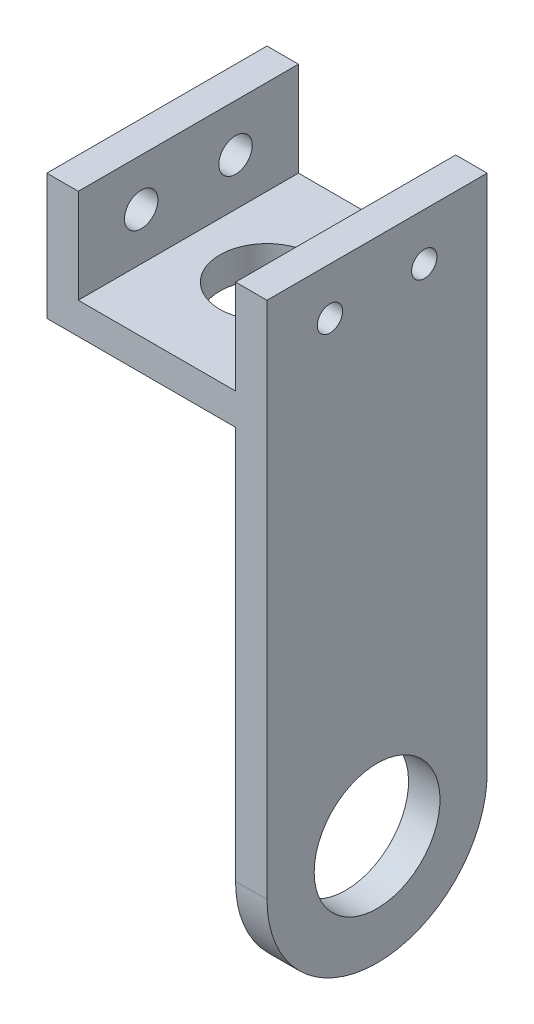
SolidWorks part; units mm, degrees
material "6061-T6 (SS)"
ref_plane "Front" through (0, 0, 0) normal (0, 0, 1) x (1, 0, 0)
ref_plane "Top" through (0, 0, 0) normal (0, 1, 0) x (1, 0, 0)
ref_plane "Right" through (0, 0, 0) normal (1, 0, 0) x (0, 0, -1)
sketch "Sketch1" plane through (0, 0, 0) normal (0, 0, 1) x (1, 0, 0)
  line L0 (0, 0) -> (6.35, 0)
  line L1 (6.35, 0) -> (6.35, 127)
  line L2 (6.35, 127) -> (0, 127)
  line L3 (0, 127) -> (0, 107.95)
  line L4 (0, 107.95) -> (-31.75, 107.95)
  line L5 (-31.75, 107.95) -> (-31.75, 127)
  line L6 (-31.75, 127) -> (-38.1, 127)
  line L7 (-38.1, 127) -> (-38.1, 101.6)
  line L8 (-38.1, 101.6) -> (0, 101.6)
  line L9 (0, 101.6) -> (0, 0)
  point P3 (3.175, 0)
  dimension "D1" = 6.35
  dimension "D2" = 101.6
  dimension "D3" = 31.75
  dimension "D4" = 6.35
  dimension "D5" = 6.35
  dimension "D6" = 19.05
  dimension "D7" = 19.05
  dimension "D8" = 6.35
extrude "Boss-Extrude1" add sketch "Sketch1" along normal blind 44.45
sketch "Sketch2" plane through (0, 0, 0) normal (-1, 0, 0) x (0, 0, 1)
  line L0 (44.45, 0) -> (0, 0) construction
  line L1 (44.45, 101.6) -> (44.45, 0) construction
  circle A0 centre (22.225, 22.225) radius 12.7
  dimension "D3" = 25.4
  dimension "D1" = 22.225
  dimension "D2" = 22.225
extrude "Cut-Extrude1" cut sketch "Sketch2" against normal blind 44.45
hole_wizard "1/4-20 Tapped Hole1" positions "Sketch3" profile "Sketch4" tap size "1/4-20" standard "ANSI Inch" end condition through all
sketch "Sketch3" plane through (0, 0, 0) normal (-1, 0, 0) x (0, 0, 1)
  line L2 (44.45, 127) -> (0, 127) construction
  line L3 (0, 127) -> (0, 107.95) construction
  point P0 (12.7, 117.475)
  point P2 (31.75, 117.475)
  dimension "D1" = 19.05
  dimension "D2" = 9.525
  dimension "D3" = 12.7
sketch "Sketch4" plane through (0, 117.475, 12.7) normal (0, 1, 0) x (0, 0, 1)
  line L0 (0, 0) -> (0, 6.35)
  line L1 (0, 6.35) -> (2.5527, 6.35)
  line L2 (2.5527, 6.35) -> (2.5527, 0)
  line L5 (2.5527, 0) -> (0, 0)
  line L11 (0, -6.35) -> (0, 107.95) construction
  dimension "Thru Tap Drill Dia." = 5.1054
  dimension "Thru Tap Drill Depth" = 6.35
cosmetic thread "Hole Thread1" parameters "D2"=6.35
cosmetic thread "Hole Thread2" parameters "D2"=6.35
sketch "Sketch5" plane through (-38.1, 0, 0) normal (-1, 0, 0) x (0, 0, 1)
  line L0 (44.45, 127) -> (0, 127) construction
  line L1 (44.45, 127) -> (44.45, 101.6) construction
  circle A0 centre (12.7, 117.475) radius 3.3782
  circle A1 centre (31.75, 117.475) radius 3.3782
  dimension "D4" = 6.7564
  dimension "D1" = 19.05
  dimension "D2" = 9.525
  dimension "D3" = 12.7
extrude "Cut-Extrude2" cut sketch "Sketch5" against normal blind 8.89
sketch "Sketch6" plane through (0, 107.95, 0) normal (0, 1, 0) x (1, 0, 0)
  line L0 (6.35, -44.45) -> (0, -44.45) construction
  line L2 (0, -44.45) -> (0, 0) construction
  circle A0 centre (-15.875, -22.225) radius 9.525
  dimension "D1" = 19.05
  dimension "D2" = 22.225
  dimension "D3" = 15.875
extrude "Cut-Extrude3" cut sketch "Sketch6" against normal blind 8.89
fillet "Fillet1" 2 edges at (3.175, 0, 44.45) (3.175, 0, 0) type full round first side face at (-12.7, 92.71, 44.45) second side face at (-12.7, 92.71, 0) middle face at (3.175, 0, 22.225)
